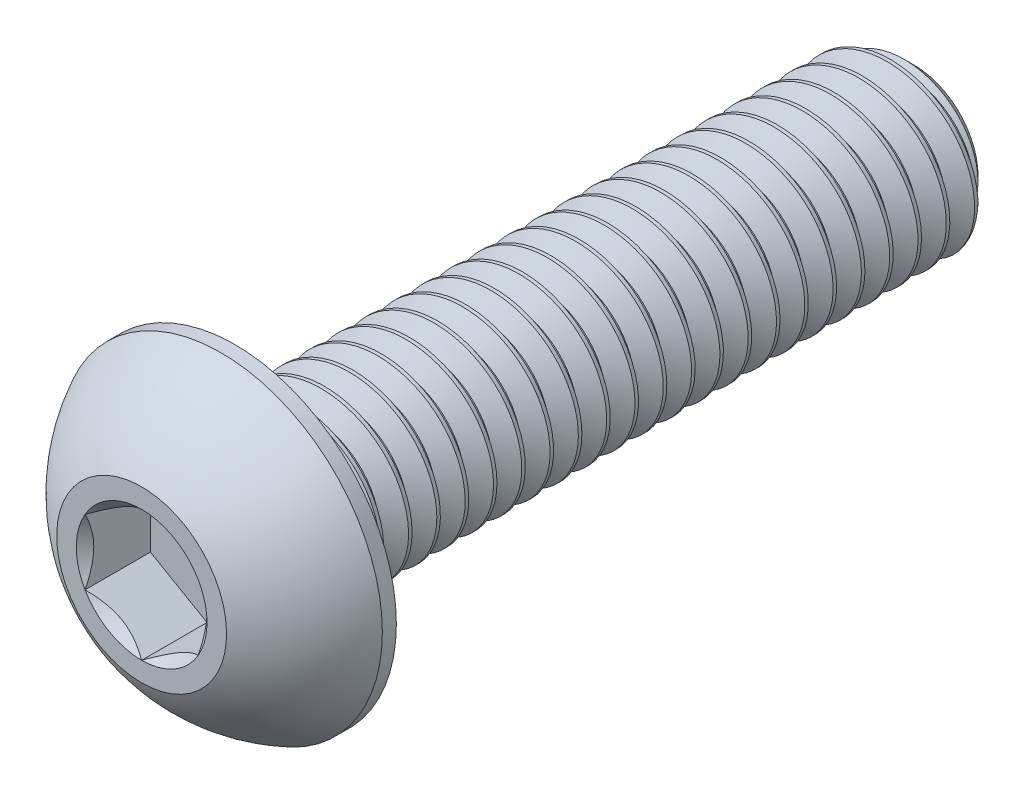
SolidWorks part; units mm, degrees
material "Alloy Steel"
ref_plane "Front" through (0, 0, 0) normal (0, 0, 1) x (1, 0, 0)
ref_plane "Top" through (0, 0, 0) normal (0, 1, 0) x (1, 0, 0)
ref_plane "Right" through (0, 0, 0) normal (1, 0, 0) x (0, 0, -1)
sketch "Sketch1" plane through (0, 0, 0) normal (1, 0, 0) x (0, 0, -1)
  line L2 (1.65, 1.5) -> (13.65, 1.5)
  line L3 (13.65, 1.5) -> (13.65, 0)
  line L4 (13.65, 0) -> (1.65, 0)
  line L6 (1.4025, 2.85) -> (1.65, 2.85) construction
  line L7 (13.65, 1.5) -> (13.65, -1.5) construction
  line L8 (0, 0) -> (1.65, 0) construction
  line L9 (1.65, 2.85) -> (1.65, -2.85) construction
  line L11 (1.65, 1.5) -> (1.65, 0)
  line L13 (0, 1) -> (0, -1) construction
  line L14 (0, 1) -> (0, 1.5) construction
  arc A3 (0, 1.5) -> (1.4025, 2.85) centre (2.7948, 0) cw construction
  dimension "D1" = 0.2475
  dimension "Head Ht" = 1.65
  dimension "Head Dia" = 5.7
  dimension "Dia" = 3
  dimension "Lg" = 12
  dimension "Hex" = 2
revolve "Revolve1" add sketch "Sketch1" angle 360 mid plane about L4
sketch "Sketch3" plane through (0, 0, -13.65) normal (0, 0, -1) x (-1, 0, 0)
  circle A0 centre (0, 0) radius 1.5
curve "Helix/Spiral1" pitch 0.5 height 12.5 radius 1.5 centre (0, 0, -13.65) axis (0, 0, 1) start towards (0, 1, 0)
sketch "Sketch2" plane through (0, 0, 0) normal (1, 0, 0) x (0, 0, -1)
  line L0 (13.65, 1.5) -> (14.0875, 1.5)
  line L1 (14.0875, 1.5) -> (13.9, 1.1752)
  line L2 (13.9, 1.1752) -> (13.8375, 1.1752)
  line L3 (13.8375, 1.1752) -> (13.65, 1.5)
  line L4 (13.7438, 1.3376) -> (13.9938, 1.3376) construction
  dimension "D1" = 60
  dimension "D2" = 0.0625
  dimension "D3" = 0.25
chamfer "Chamfer1" distance 0.375 angle 45 1 edges at (0, 1.5, -13.65)
sweep "Cut-Sweep1" cut profiles "Sketch2" path "Helix/Spiral1" align with end faces yes
sketch "Sketch7" plane through (0, 0, 0) normal (1, 0, 0) x (0, 0, -1)
  line L6 (1.4025, 2.85) -> (1.65, 2.85) construction
  line L8 (0, 0) -> (1.65, 0) construction
  line L11 (1.65, 2.85) -> (1.65, -2.85) construction
  line L12 (1.4025, 2.85) -> (1.65, 2.85)
  line L13 (0, 0) -> (1.65, 0)
  line L14 (0, 1) -> (0, -1) construction
  line L15 (1.65, 2.85) -> (1.65, 0)
  line L16 (0, 1.5) -> (0, 0)
  arc A2 (1.4025, 2.85) -> (0, 1.5) centre (2.7948, 0) ccw construction
  arc A3 (1.4025, 2.85) -> (0, 1.5) centre (2.7948, 0) ccw
revolve "Revolve2" add sketch "Sketch7" angle 360 mid plane about L13
sketch "Sketch5" plane through (0, 0, 0) normal (0, 0, 1) x (1, 0, 0)
  line L1 (1, -0.5774) -> (1, 0.5774)
  line L2 (1, 0.5774) -> (0, 1.1547)
  line L3 (0, 1.1547) -> (-1, 0.5774)
  line L4 (-1, 0.5774) -> (-1, -0.5774)
  line L5 (-1, -0.5774) -> (0, -1.1547)
  line L6 (0, -1.1547) -> (1, -0.5774)
  circle A0 centre (0, 0) radius 1 construction
extrude "Cut-Extrude2" cut sketch "Sketch5" against normal blind 1.155
sketch "Sketch6" plane through (0, 0, 0) normal (0, 0, 1) x (1, 0, 0)
  circle A0 centre (0, 0) radius 1.1547
extrude "Cut-Extrude3" cut sketch "Sketch6" against normal blind 1.155 draft 45
sketch "Sketch9" [suppressed] plane through (0, 0, -4.2164) normal (0, 0, 1) x (1, 0, 0)
  circle A2 centre (0, 0) radius 3.9687
extrude "Boss-Extrude2" [suppressed] add sketch "Sketch9" against normal offset from surface (9.525 mm away) 28.575 up to face at (0, 1.125, -13.65)
sketch "Sketch10" plane through (0, 0, 0) normal (1, 0, 0) x (0, 0, -1)
  line L0 (13.65, 1.5) -> (13.65, -1.5) construction
  point P0 (12.9, -1.5)
  dimension "D1" = 0.75
equation "\"D3@Helix/Spiral1\" = \"Lg@Sketch1\" + \"D4@Helix/Spiral1\""
equation "\"D2@Sketch2\" = \"D4@Helix/Spiral1\" * .125"
equation "\"D3@Sketch2\" = \"D4@Helix/Spiral1\" * .5"
equation "\"D1@Chamfer1\" = \"D4@Helix/Spiral1\" * .75"
equation "\"D1@Cut-Extrude2\" = \"Head Ht@Sketch1\" * .7"
equation "\"D1@Sketch1\" = \"Head Ht@Sketch1\" * .15"
equation "\"D1@Sketch10\" = \"D4@Helix/Spiral1\" * 1.5"
equation "\"D1@Cut-Extrude3\" = \"D1@Cut-Extrude2\""
